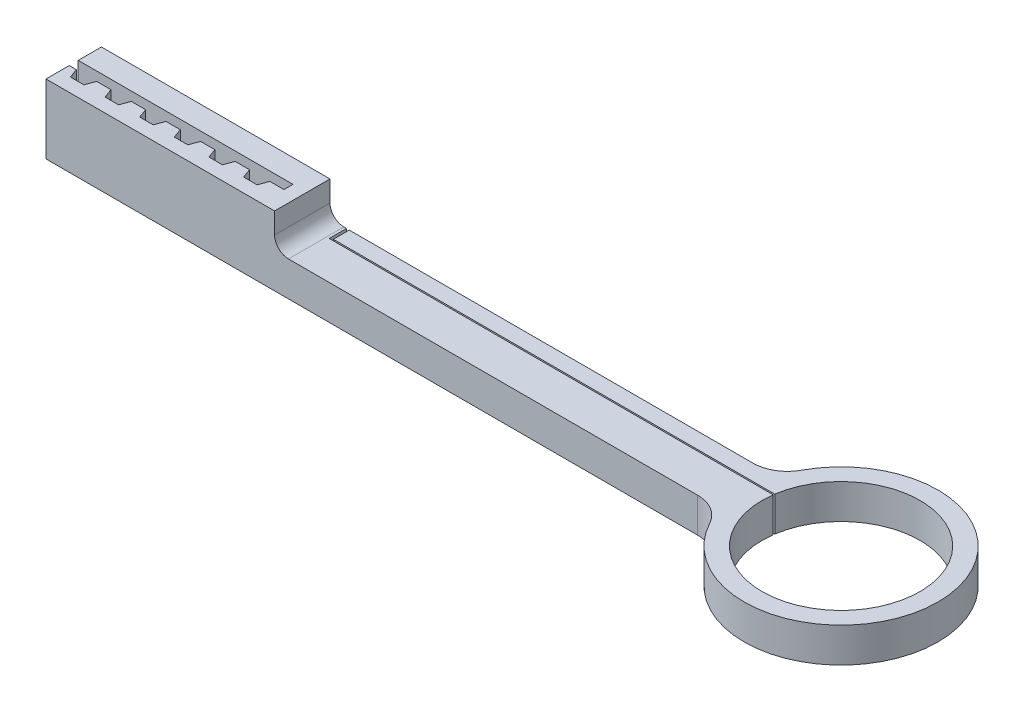
SolidWorks part; units mm, degrees
ref_plane "Спереди" through (0, 0, 0) normal (0, 0, 1) x (1, 0, 0)
ref_plane "Сверху" through (0, 0, 0) normal (0, 1, 0) x (1, 0, 0)
ref_plane "Справа" through (0, 0, 0) normal (1, 0, 0) x (0, 0, -1)
sketch "Эскиз1" plane through (0, 0, 0) normal (0, 1, 0) x (1, 0, 0)
  circle A0 centre (0, 0) radius 11.4
  circle A1 centre (0, 0) radius 14
  dimension "D1" = 22.8
  dimension "D2" = 28
extrude "ring" add sketch "Эскиз1" along normal blind 5
sketch "Эскиз2" plane through (0, 0, 0) normal (0, 1, 0) x (1, 0, 0)
  line L0 (34.0214, 0) -> (-42.1067, 0) construction
  line L1 (-10.7819, 4) -> (-10.7819, -4) construction
  line L2 (-10.7819, 4) -> (-110.7819, 4)
  line L4 (-10.7819, -4) -> (-110.7819, -4)
  line L5 (-110.7819, 4) -> (-110.7819, -4)
  circle A0 centre (0, 0) radius 11.5 construction
  arc A1 (-10.7819, 4) -> (-10.7819, -4) centre (0, 0) ccw
  point P9 (-10.7819, 0)
  dimension "D3" = 23
  dimension "D2" = 8
  dimension "D4" = 100
extrude "stick" add sketch "Эскиз2" along normal blind 5
sketch "Эскиз3" plane through (0, 0, 0) normal (0, 1, 0) x (1, 0, 0)
  line L0 (-110.7819, -4) -> (-13.4164, -4) construction
  line L1 (-110.7819, 4) -> (-77.7819, 4)
  line L2 (-110.7819, 4) -> (-110.7819, -4)
  line L3 (-110.7819, -4) -> (-77.7819, -4)
  line L4 (-77.7819, 4) -> (-77.7819, -4)
  dimension "D1" = 33
extrude "key" add sketch "Эскиз3" along normal blind 10
fillet "Скругление1" radius 5 2 edges at (-13.4164, 2.5, 4) (-13.4164, 2.5, -4)
ref_plane "Плоскость1" through (0, 2.5, 0) normal (0, 1, 0) x (-1, 0, 0)
sketch "Эскиз4" plane through (0, 2.5, 0) normal (0, 1, 0) x (1, 0, 0)
  line L0 (-110.7819, 0) -> (-77.7819, 0) construction
  line L1 (-110.7819, 4) -> (-110.7819, -4) construction
  line L2 (-77.7819, -4) -> (-77.7819, 4) construction
  line L3 (-110.7819, 0.65) -> (-80.2819, 0.65)
  line L4 (-109.2569, -2) -> (-107.3069, -2)
  line L5 (-109.5437, -0.65) -> (-90.7013, -0.65) construction
  line L6 (-109.7483, -0.65) -> (-109.2569, -2) construction
  line L7 (-109.7483, -0.65) -> (-109.2569, -2)
  line L8 (-107.3069, -2) -> (-106.8156, -0.65)
  line L9 (-108.2819, 0.7157) -> (-108.2819, -3.7603) construction
  line L10 (-109.7483, -0.65) -> (-110.7819, -0.65)
  line L11 (-106.8156, -0.65) -> (-105.7819, -0.65)
  line L12 (-110.7819, 0.65) -> (-110.7819, -0.65)
  line L13 (-104.7483, -0.65) -> (-105.7819, -0.65)
  line L14 (-104.2569, -2) -> (-102.3069, -2)
  line L15 (-102.3069, -2) -> (-101.8156, -0.65)
  line L16 (-101.8156, -0.65) -> (-100.7819, -0.65)
  line L17 (-104.7483, -0.65) -> (-104.2569, -2)
  line L18 (-99.7483, -0.65) -> (-100.7819, -0.65)
  line L19 (-99.2569, -2) -> (-97.3069, -2)
  line L20 (-97.3069, -2) -> (-96.8156, -0.65)
  line L21 (-96.8156, -0.65) -> (-95.7819, -0.65)
  line L22 (-99.7483, -0.65) -> (-99.2569, -2)
  line L24 (-94.7483, -0.65) -> (-95.7819, -0.65)
  line L25 (-94.2569, -2) -> (-92.3069, -2)
  line L26 (-92.3069, -2) -> (-91.8156, -0.65)
  line L27 (-91.8156, -0.65) -> (-90.7819, -0.65)
  line L28 (-94.7483, -0.65) -> (-94.2569, -2)
  line L43 (-89.7483, -0.65) -> (-90.7819, -0.65)
  line L44 (-89.2569, -2) -> (-87.3069, -2)
  line L45 (-87.3069, -2) -> (-86.8156, -0.65)
  line L46 (-86.8156, -0.65) -> (-85.7819, -0.65)
  line L47 (-89.7483, -0.65) -> (-89.2569, -2)
  line L48 (-84.7483, -0.65) -> (-85.7819, -0.65)
  line L49 (-84.2569, -2) -> (-82.3069, -2)
  line L50 (-82.3069, -2) -> (-81.8156, -0.65)
  line L51 (-81.8156, -0.65) -> (-80.7819, -0.65)
  line L52 (-84.7483, -0.65) -> (-84.2569, -2)
  line L53 (-80.7819, -0.65) -> (-80.2819, -0.65)
  line L54 (-80.2819, 0.65) -> (-80.2819, -0.65)
  point P12 (-108.2819, -2)
  dimension "D1" = 1.95
  dimension "D2" = 0.65
  dimension "D3" = 0.65
  dimension "D4" = 1.35
  dimension "D5" = 110
  dimension "D6" = 5
  dimension "D7" = 40
  dimension "D8" = 0.5
fillet "Скругление5" radius 2 1 edges at (-77.7819, 5, 0)
extrude "key hole" cut sketch "Эскиз4" against normal through all and the other way through all
sketch "Эскиз5" plane through (0, 0, 0) normal (0, -1, 0) x (1, 0, 0)
  line L0 (0, 0) -> (-70.3859, 0) construction
  line L1 (-75.4, -4) -> (-75.4, -1.5)
  line L3 (-75.4, -1.5) -> (0, -1.5)
  line L4 (0, -1.5) -> (0, -1.7)
  line L5 (0, -1.7) -> (-75, -1.7)
  line L6 (-75, -1.7) -> (-75, -4)
  line L7 (-75, -4) -> (-75.4, -4)
  line L8 (-16.7332, -4) -> (-110.7819, -4) construction
  dimension "D1" = 0.2
  dimension "D2" = 0.4
  dimension "D3" = 75
  dimension "D4" = 1.5
extrude "correction hole 1" cut sketch "Эскиз5" against normal through all
sketch "Эскиз6" plane through (0, 10, 0) normal (0, 1, 0) x (1, 0, 0)
  line L1 (-80.2819, 0.65) -> (-79.7819, 0.65)
  line L2 (-80.2819, 0.65) -> (-80.2819, -0.65)
  line L3 (-80.2819, -0.65) -> (-79.7819, -0.65)
  line L4 (-79.7819, 0.65) -> (-79.7819, -0.65)
  dimension "D1" = 0.5
extrude "correction hole" cut sketch "Эскиз6" against normal through all
sketch "Эскиз7" plane through (0, 5, 0) normal (0, 1, 0) x (-1, 0, 0)
  point P0 (0, 0)
sketch "Эскиз8" plane through (0, 10, 0) normal (0, 1, 0) x (1, 0, 0)
  line L1 (-110.7819, 4) -> (0, 4)
  line L2 (-110.7819, 4) -> (-110.7819, 0)
  line L3 (-110.7819, 0) -> (0, 0)
  line L4 (0, 4) -> (0, 0)
